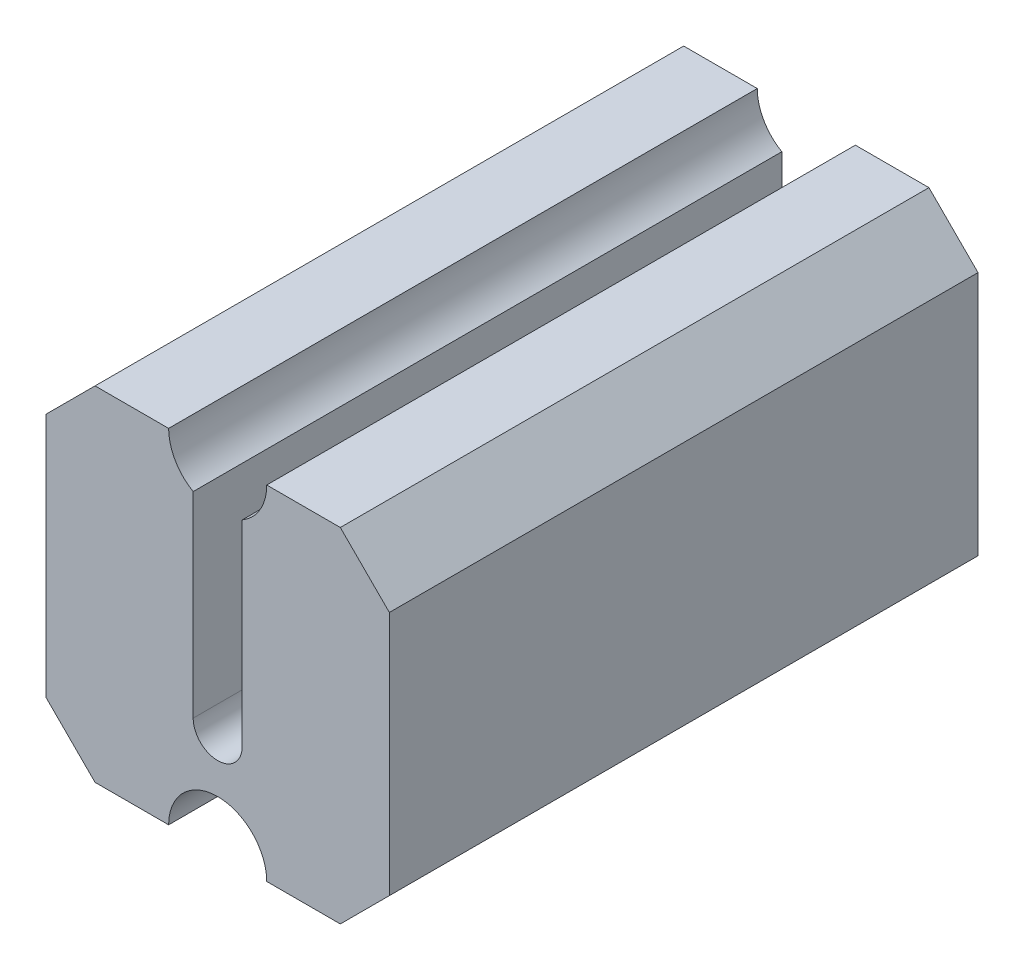
SolidWorks part; units mm, degrees
ref_plane "Front Plane" through (0, 0, 0) normal (0, 0, 1) x (1, 0, 0)
ref_plane "Top Plane" through (0, 0, 0) normal (0, 1, 0) x (1, 0, 0)
ref_plane "Right Plane" through (0, 0, 0) normal (1, 0, 0) x (0, 0, -1)
sketch "Sketch1" plane through (0, 0, 0) normal (0, 0, 1) x (1, 0, 0)
  line L0 (125, 175) -> (50, 175)
  line L1 (-125, -175) -> (-50, -175)
  line L2 (-175, -125) -> (-175, 125)
  line L3 (0, 0) -> (0, -70.9541) construction
  line L4 (175, -125) -> (175, 125)
  line L5 (-175, 0) -> (175, 0) construction
  line L6 (0, -93.3013) -> (0, -125) construction
  line L7 (-125, 175) -> (-125, -175) construction
  line L8 (-25, 131.6987) -> (-25, -68.3013)
  line L9 (-175, 125) -> (-25, 125) construction
  line L10 (125, 175) -> (125, -175) construction
  line L11 (-175, -125) -> (175, -125) construction
  line L12 (-125, 175) -> (-175, 125)
  line L13 (125, 175) -> (175, 125)
  line L14 (125, -175) -> (175, -125)
  line L15 (-125, -175) -> (-175, -125)
  line L16 (50, -175) -> (125, -175)
  line L17 (-50, 175) -> (-125, 175)
  line L18 (25, 131.6987) -> (25, -68.3013)
  line L19 (25, 125) -> (175, 125) construction
  arc A0 (-50, 175) -> (-25, 131.6987) centre (0, 175) ccw
  arc A1 (50, -175) -> (-50, -175) centre (0, -175) ccw
  arc A2 (-25, -68.3013) -> (25, -68.3013) centre (0, -68.3013) ccw
  arc A3 (25, 131.6987) -> (50, 175) centre (0, 175) ccw
  dimension "D1" = 350
  dimension "D5" = 50
  dimension "D6" = 25
  dimension "D8" = 50
  dimension "D2" = 350
  dimension "D3" = 50
  dimension "D4" = 50
  dimension "D7" = 200
  dimension "D9" = 0
  dimension "D10" = 75
  dimension "D11" = 75
  dimension "D12" = 100
  dimension "D13" = 50
  dimension "D14" = 0
extrude "Boss-Extrude1" add sketch "Sketch1" along normal blind 400 and the other way blind 200
ref_plane "Plane1" through (0, -175, 0) normal (0, -1, 0) x (-1, 0, 0)
